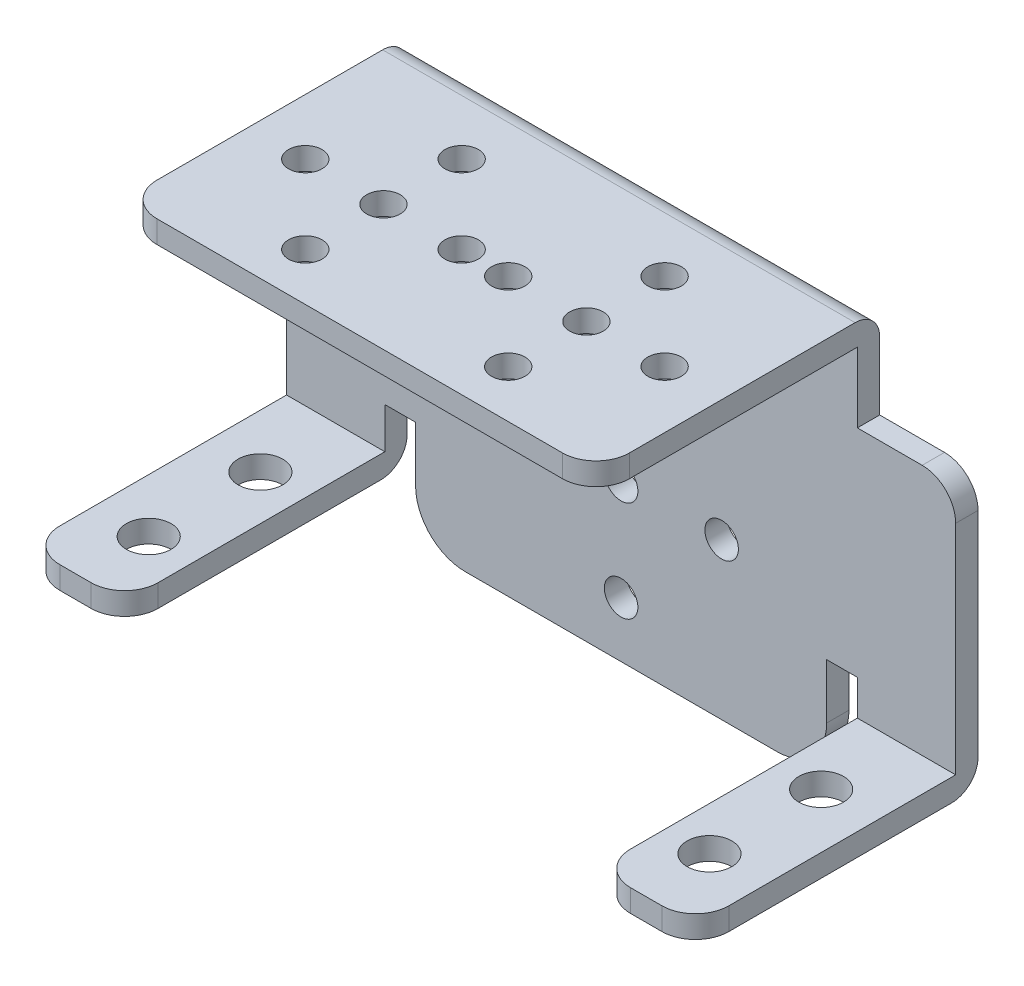
SolidWorks part; units mm, degrees
note: The reader was unsure of these and kept them because the rebuilt part matched: shared geometry of "Sketch1<3>", "Sketch1<4>".
ref_plane "前视基准面" through (0, 0, 0) normal (0, 0, 1) x (1, 0, 0)
ref_plane "上视基准面" through (0, 0, 0) normal (0, 1, 0) x (1, 0, 0)
ref_plane "右视基准面" through (0, 0, 0) normal (1, 0, 0) x (0, 0, -1)
sketch "Sketch1" plane through (0, 0, 0) normal (0, 0, 1) x (1, 0, 0)
  line L0 (-21.15, 16.48) -> (21.15, 16.48)
  line L1 (-21.15, 18.48) -> (21.15, 18.48)
  line L2 (-21.15, 18.48) -> (-21.15, -14.78)
  line L3 (-4.3498, -18.48) -> (13.96, -18.48)
  line L4 (21.15, 18.48) -> (21.15, -14.28)
  line L5 (-13.96, -18.48) -> (-4.3498, -18.48)
  line L6 (-18.4, -9.12) -> (18.4, -9.12)
  line L7 (-18.4, -9.12) -> (-18.4, -14.04)
  line L8 (-13.96, -18.48) -> (13.96, -18.48)
  line L9 (18.4, -9.12) -> (18.4, -14.04)
  line L10 (-4.3498, -18.48) -> (13.96, -18.48)
  line L11 (18.4, -9.12) -> (21.15, -9.12)
  line L12 (21.15, 10.22) -> (29.95, 10.22)
  line L13 (21.15, 10.22) -> (21.15, -14.28)
  line L14 (21.15, -14.28) -> (29.95, -14.28)
  line L15 (29.95, 10.22) -> (29.95, -14.28)
  line L16 (-29.95, 9.72) -> (-21.15, 9.72)
  line L17 (-29.95, 9.72) -> (-29.95, -14.78)
  line L18 (-29.95, -14.78) -> (-21.15, -14.78)
  line L19 (-21.15, 9.72) -> (-21.15, -14.78)
  line L20 (18.4, -9.12) -> (21.15, -9.12)
  line L21 (18.4, -9.12) -> (21.15, -9.12)
  line L22 (-18.4, -9.12) -> (-21.15, -9.12)
  line L24 (21.15, -12.28) -> (29.95, -12.28)
  line L25 (21.15, -12.28) -> (21.15, -14.28)
  line L26 (21.15, -14.28) -> (29.95, -14.28)
  line L27 (29.95, -12.28) -> (29.95, -14.28)
  line L28 (-29.95, -12.78) -> (-21.15, -12.78)
  line L29 (-29.95, -12.78) -> (-29.95, -14.78)
  line L30 (-29.95, -14.78) -> (-21.15, -14.78)
  line L31 (-21.15, -12.78) -> (-21.15, -14.78)
  arc A0 (-13.96, -18.48) -> (-18.4, -14.04) centre (-13.96, -14.04) cw
  arc A1 (13.96, -18.48) -> (18.4, -14.04) centre (13.96, -14.04) ccw
  point P20 (18.4, -18.48)
  point P30 (-25.55, -14.78)
  point P32 (-25.55, -12.78)
  dimension "D9" = 4.44
  dimension "D10" = 4.44
  dimension "D2" = 42.3
  dimension "D3" = 21.15
  dimension "D4" = 18.48
  dimension "D5" = 2
  dimension "D6" = 9.36
  dimension "D7" = 36.8
  dimension "D8" = 18.4
  dimension "D11" = 18.48
  dimension "D12" = 24.5
  dimension "D13" = 24.5
  dimension "D14" = 8.8
  dimension "D15" = 8.8
  dimension "D16" = 32.76
  dimension "D17" = 33.26
  dimension "D18" = 2
  dimension "D19" = 2
extrude "Boss-Extrude1" add sketch "Sketch1" along normal blind 2 contours L22 L6 L11 L4 L0 L2 | L3 A1 L9 L6 L7 A0 L5 | L17 L28 L19 L2 L16 | L4 L24 L15 L12
extrude "Boss-Extrude2" add sketch "Sketch1<3>" along normal blind 25.4 contours L4 L1 L2 L0
sketch "Sketch1<3>" plane through (0, 0, 0) normal (0, 0, 1) x (1, 0, 0) same geometry as "Sketch1"
extrude "Boss-Extrude3" add sketch "Sketch1<4>" along normal blind 25.3 contours L28 L17 L18 L2 | L24 L13 L14 L15
sketch "Sketch1<4>" plane through (0, 0, 0) normal (0, 0, 1) x (1, 0, 0) same geometry as "Sketch1"
fillet "Fillet13" radius 3 1 edges at (-21.15, -13.78, 25.3)
fillet "Fillet14" radius 3 1 edges at (-29.95, -13.78, 25.3)
fillet "Fillet15" radius 3 1 edges at (29.95, -13.28, 25.3)
fillet "Fillet16" radius 3 1 edges at (21.15, -13.28, 25.3)
fillet "Fillet18" radius 3 1 edges at (21.15, 17.48, 25.4)
fillet "Fillet19" radius 3 1 edges at (-21.15, 17.48, 25.4)
fillet "Fillet20" radius 3 1 edges at (29.95, 10.22, 1)
fillet "Fillet21" radius 3 1 edges at (-29.95, 9.72, 1)
sketch "Sketch2" plane through (0, -14.28, 0) normal (0, -1, 0) x (1, 0, 0)
  line L0 (24.15, 25.3) -> (26.95, 25.3) construction
  line L1 (25.05, 19.14) -> (25.05, 9.14) construction
  line L2 (21.15, 22.3) -> (21.15, 0) construction
  line L3 (-26.95, 25.3) -> (-24.15, 25.3) construction
  line L5 (-21.15, 22.3) -> (-21.15, 0) construction
  circle A0 centre (25.05, 19.14) radius 2
  circle A1 centre (25.05, 9.14) radius 2
  circle A2 centre (-25.15, 19.14) radius 2
  circle A3 centre (-25.15, 9.14) radius 2
  dimension "D1" = 4
  dimension "D2" = 4
  dimension "D7" = 4
  dimension "D8" = 4
  dimension "D3" = 6.16
  dimension "D4" = 10
  dimension "D5" = 3.9
  dimension "D9" = 6.16
  dimension "D10" = 4
  dimension "D11" = 10
fillet "Fillet24" radius 2.36 1 edges at (-25.55, -14.78, 0)
fillet "Fillet25" radius 2.36 1 edges at (25.55, -14.28, 0)
fillet "Fillet26" radius 2.2 1 edges at (0, 18.48, 0)
extrude "Cut-Extrude1" cut sketch "Sketch2" against normal mid plane 20
sketch "Sketch3" plane through (0, 18.48, 0) normal (0, 1, 0) x (1, 0, 0)
  line L0 (21.15, -2.2) -> (-21.15, -2.2) construction
  line L1 (-21.15, -22.4) -> (-21.15, -2.2) construction
  line L2 (-18.15, -25.4) -> (18.15, -25.4) construction
  line L3 (21.15, -22.4) -> (21.15, -2.2) construction
  line L4 (0, -34.8199) -> (0, 24.3344) construction
  circle A5 centre (-9.1346, -14.14) radius 1.5
  circle A6 centre (-9.1346, -7.14) radius 1.5
  circle A7 centre (-2.1346, -14.14) radius 1.5
  circle A8 centre (-9.1346, -21.14) radius 1.5
  circle A9 centre (-16.1346, -14.14) radius 1.5
  circle A10 centre (9.0346, -14.14) radius 1.5
  circle A11 centre (9.0346, -7.14) radius 1.5
  circle A12 centre (16.0346, -14.14) radius 1.5
  circle A13 centre (9.0346, -21.14) radius 1.5
  circle A14 centre (2.0346, -14.14) radius 1.5
  point P31 (-9.1346, -14.14)
  point P34 (9.0346, -14.14)
  point P43 (9.0346, -14.14)
  dimension "D2" = 7
  dimension "D7" = 3
  dimension "D8" = 3
  dimension "D3" = 3
  dimension "D4" = 3
  dimension "D5" = 4
  dimension "D6" = 12.0154
  dimension "D10" = 4.94
  dimension "D11" = 23.2
  dimension "D12" = 42.3
  dimension "D9" = 4
extrude "Cut-Extrude2" cut sketch "Sketch3" against normal blind 10
sketch "Sketch4" plane through (0, 0, 0) normal (0, 0, -1) x (-1, 0, 0)
  line L0 (-21.15, -9.12) -> (-18.4, -9.12) construction
  line L1 (18.4, -9.12) -> (21.15, -9.12) construction
  line L2 (-21.15, -9.12) -> (-18.4, -9.12)
  line L3 (18.4, -9.12) -> (21.15, -9.12)
  line L4 (-21.15, 18.48) -> (21.15, 18.48) construction
  line L5 (-21.15, 18.48) -> (21.15, 18.48)
  circle A0 centre (0, 4.48) radius 1.5
  circle A1 centre (0, -4.52) radius 1.5
  circle A2 centre (0, -13.52) radius 1.5
  circle A3 centre (9, -4.52) radius 1.5
  circle A4 centre (-9, -4.52) radius 1.5
  dimension "D1" = 3
  dimension "D2" = 3
  dimension "D4" = 3
  dimension "D6" = 3
  dimension "D8" = 3
  dimension "D3" = 9
  dimension "D5" = 9
  dimension "D7" = 9
  dimension "D9" = 9
  dimension "D10" = 23
extrude "Cut-Extrude3" cut sketch "Sketch4" against normal blind 10 contours A4 | A0 | A3 | A2 | A1
